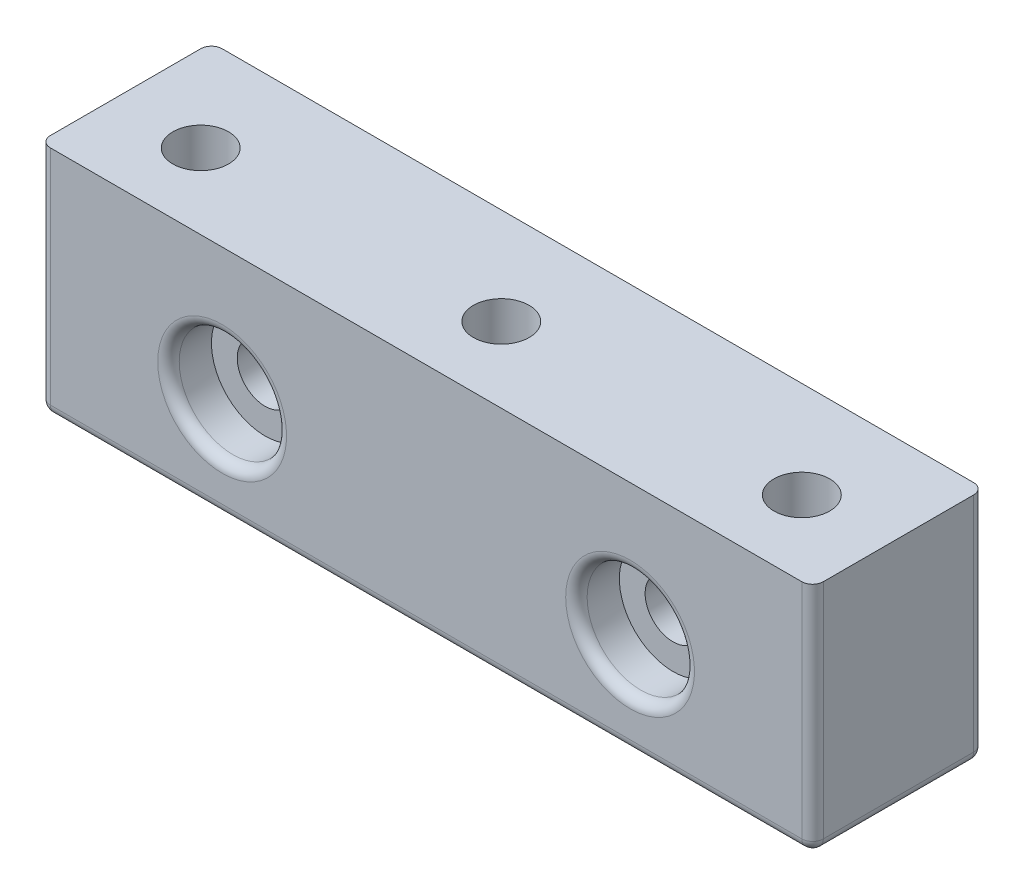
SolidWorks part; units mm, degrees
material "ABS"
ref_plane "Front Plane" through (0, 0, 0) normal (0, 0, 1) x (1, 0, 0)
ref_plane "Top Plane" through (0, 0, 0) normal (0, 1, 0) x (1, 0, 0)
ref_plane "Right Plane" through (0, 0, 0) normal (1, 0, 0) x (0, 0, -1)
sketch "Sketch1" plane through (0, 0, 0) normal (0, 0, 1) x (1, 0, 0)
  line L0 (36, -1.375) -> (-36, -1.375) construction
  line L1 (-36, -10.875) -> (36, -10.875)
  line L2 (-36, -10.875) -> (-36, 10.875)
  line L3 (-36, 10.875) -> (36, 10.875)
  line L4 (36, -10.875) -> (36, 10.875)
  line L5 (-36, -10.875) -> (36, 10.875) construction
  line L6 (-36, 10.875) -> (36, -10.875) construction
  line L7 (0, 10.875) -> (0, -10.875) construction
  circle A0 centre (-19, -1.375) radius 2.6
  circle A1 centre (19, -1.375) radius 2.6
  point P0 (0, 0)
  dimension "D3" = 5.2
  dimension "D4" = 38
  dimension "D1" = 72
  dimension "D2" = 21.75
  dimension "D5" = 12.25
extrude "Boss-Extrude1" add sketch "Sketch1" along normal blind 16
sketch "Sketch2" plane through (0, 0, 16) normal (0, 0, 1) x (1, 0, 0)
  circle A0 centre (-19, -1.375) radius 5
  circle A1 centre (19, -1.375) radius 5
  dimension "D1" = 10
extrude "Cut-Extrude1" cut sketch "Sketch2" against normal blind 4
sketch "Sketch3" plane through (0, 10.875, 0) normal (0, 1, 0) x (1, 0, 0)
  line L0 (-36, -9) -> (36, -9) construction
  line L3 (0, 0) -> (0, -16) construction
  line L4 (36, -16) -> (-36, -16) construction
  line L5 (36, 0) -> (-36, 0) construction
  line L6 (-36, -16) -> (-36, 0) construction
  line L7 (36, -16) -> (36, 0) construction
  circle A0 centre (0, -9) radius 2.6
  circle A1 centre (-28, -9) radius 2.6
  circle A2 centre (28, -9) radius 2.6
  dimension "D1" = 5.2
  dimension "D2" = 28
  dimension "D3" = 9
extrude "Cut-Extrude2" cut sketch "Sketch3" against normal up to surface (21.75 mm away) up to face at (0, -10.875, 8)
sketch "Sketch4" plane through (0, -10.875, 0) normal (0, -1, 0) x (1, 0, 0)
  circle A0 centre (-28, 9) radius 5
  circle A1 centre (0, 9) radius 5
  circle A2 centre (28, 9) radius 5
  dimension "D1" = 10
extrude "Cut-Extrude3" cut sketch "Sketch4" against normal blind 1
fillet "Fillet1" radius 1 13 edges at (24, -1.375, 16) (-14, -1.375, 16) (-36, 0, 16) (36, 0, 16) (36, 0, 0) (-36, 0, 0) (-36, -10.875, 8) (36, -10.875, 8) (0, -10.875, 0) (0, -10.875, 16) (33, -10.875, 9) (5, -10.875, 9) (-23, -10.875, 9)
